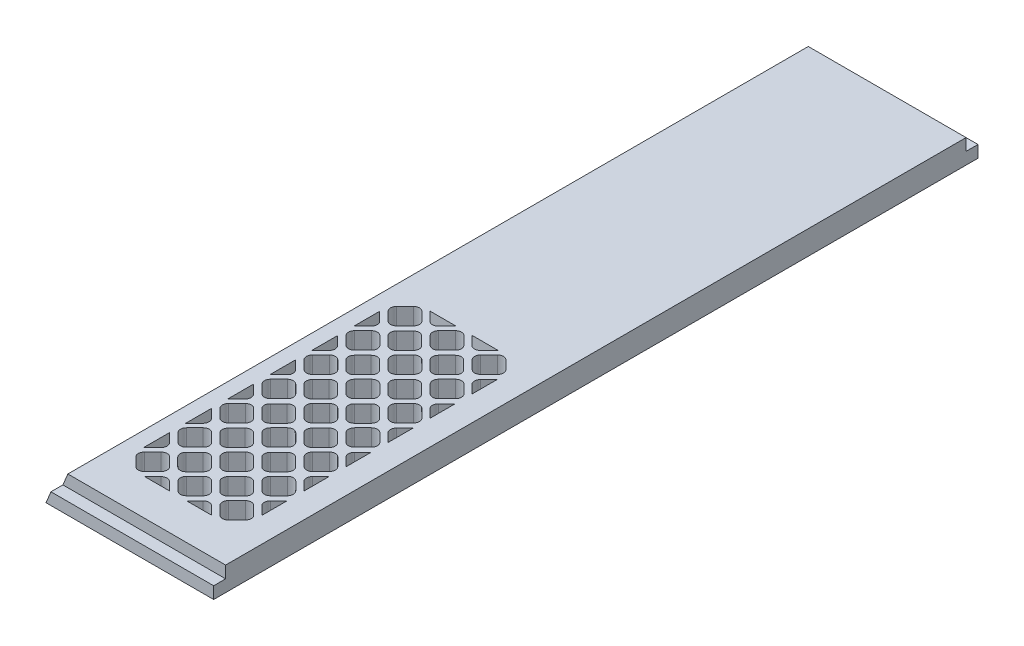
SolidWorks part; units mm, degrees
ref_plane "Front Plane" through (0, 0, 0) normal (0, 0, 1) x (1, 0, 0)
ref_plane "Top Plane" through (0, 0, 0) normal (0, 1, 0) x (1, 0, 0)
ref_plane "Right Plane" through (0, 0, 0) normal (1, 0, 0) x (0, 0, -1)
sketch "Sketch1" plane through (0, 0, 0) normal (0, 0, 1) x (1, 0, 0)
  line L0 (0, 0) -> (5.2605, 12.7)
  line L1 (5.2605, 12.7) -> (89.154, 12.7)
  line L2 (89.154, 12.7) -> (89.154, 0)
  line L3 (89.154, 0) -> (0, 0)
  dimension "D1" = 12.7
  dimension "D2" = 89.154
  dimension "D3" = 67.5
extrude "Boss-Extrude1" add sketch "Sketch1" along normal blind 406.4
sketch "Sketch2" plane through (0, 12.7, 0) normal (0, -1, 0) x (1, 0, 0)
  line L0 (0, 406.4) -> (0, 0) construction
  line L1 (0, 6.35) -> (89.154, 6.35)
  line L2 (0, 6.35) -> (0, 0)
  line L3 (0, 0) -> (89.154, 0)
  line L4 (89.154, 6.35) -> (89.154, 0)
  line L5 (89.154, 406.4) -> (89.154, 0) construction
  line L6 (0, 406.4) -> (89.154, 406.4)
  line L7 (0, 406.4) -> (0, 400.05)
  line L8 (0, 400.05) -> (89.154, 400.05)
  line L9 (89.154, 406.4) -> (89.154, 400.05)
  dimension "D1" = 6.35
  dimension "D2" = 6.35
extrude "Cut-Extrude1" cut sketch "Sketch2" along normal blind 6.35
sketch "Sketch3" plane through (0, 0, 0) normal (0, -1, 0) x (1, 0, 0)
  line L90 (0, 203.2) -> (89.154, 203.2) construction
  line L91 (0, 406.4) -> (0, 0) construction
  line L221 (89.154, 406.4) -> (89.154, 0) construction
  line L222 (13.3842, 233.4919) -> (17.8743, 229.0018)
  line L223 (17.8743, 246.8637) -> (13.3842, 242.3736)
  line L235 (13.3842, 255.8439) -> (17.8743, 251.3538)
  line L236 (17.8743, 269.2157) -> (13.3842, 264.7256)
  line L237 (13.3842, 278.1959) -> (17.8743, 273.7058)
  line L238 (17.8743, 291.5677) -> (13.3842, 287.0776)
  line L239 (13.3842, 300.5479) -> (17.8743, 296.0578)
  line L240 (17.8743, 313.9197) -> (13.3842, 309.4296)
  line L241 (13.3842, 322.8999) -> (17.8743, 318.4098)
  line L242 (17.8743, 336.2717) -> (13.3842, 331.7816)
  line L243 (13.3842, 345.2519) -> (17.8743, 340.7618)
  line L244 (17.8743, 358.6237) -> (13.3842, 354.1336)
  line L245 (13.3842, 367.6039) -> (17.8743, 363.1138)
  line L246 (71.4599, 229.0018) -> (75.9093, 233.4512)
  line L247 (49.1079, 229.0018) -> (53.598, 233.4919)
  line L248 (58.0882, 233.4919) -> (62.5783, 229.0018)
  line L249 (26.7559, 229.0018) -> (31.246, 233.4919)
  line L250 (35.7362, 233.4919) -> (40.2263, 229.0018)
  line L251 (71.4599, 251.3538) -> (75.9093, 255.8032)
  line L252 (75.9093, 242.4143) -> (71.4599, 246.8637)
  line L253 (49.1079, 251.3538) -> (53.598, 255.8439)
  line L254 (53.598, 242.3736) -> (49.1079, 246.8637)
  line L255 (62.5783, 246.8637) -> (58.0882, 242.3736)
  line L256 (58.0882, 255.8439) -> (62.5783, 251.3538)
  line L257 (26.7559, 251.3538) -> (31.246, 255.8439)
  line L258 (31.246, 242.3736) -> (26.7559, 246.8637)
  line L259 (40.2263, 246.8637) -> (35.7362, 242.3736)
  line L260 (35.7362, 255.8439) -> (40.2263, 251.3538)
  line L261 (71.4599, 273.7058) -> (75.9093, 278.1552)
  line L262 (75.9093, 264.7663) -> (71.4599, 269.2157)
  line L263 (49.1079, 273.7058) -> (53.598, 278.1959)
  line L264 (53.598, 264.7256) -> (49.1079, 269.2157)
  line L265 (62.5783, 269.2157) -> (58.0882, 264.7256)
  line L266 (58.0882, 278.1959) -> (62.5783, 273.7058)
  line L267 (26.7559, 273.7058) -> (31.246, 278.1959)
  line L268 (31.246, 264.7256) -> (26.7559, 269.2157)
  line L269 (40.2263, 269.2157) -> (35.7362, 264.7256)
  line L270 (35.7362, 278.1959) -> (40.2263, 273.7058)
  line L271 (71.4599, 296.0578) -> (75.9093, 300.5072)
  line L272 (75.9093, 287.1183) -> (71.4599, 291.5677)
  line L273 (49.1079, 296.0578) -> (53.598, 300.5479)
  line L274 (53.598, 287.0776) -> (49.1079, 291.5677)
  line L275 (62.5783, 291.5677) -> (58.0882, 287.0776)
  line L276 (58.0882, 300.5479) -> (62.5783, 296.0578)
  line L277 (26.7559, 296.0578) -> (31.246, 300.5479)
  line L278 (31.246, 287.0776) -> (26.7559, 291.5677)
  line L279 (40.2263, 291.5677) -> (35.7362, 287.0776)
  line L280 (35.7362, 300.5479) -> (40.2263, 296.0578)
  line L281 (71.4599, 318.4098) -> (75.9093, 322.8592)
  line L282 (75.9093, 309.4703) -> (71.4599, 313.9197)
  line L283 (49.1079, 318.4098) -> (53.598, 322.8999)
  line L284 (53.598, 309.4296) -> (49.1079, 313.9197)
  line L285 (62.5783, 313.9197) -> (58.0882, 309.4296)
  line L286 (58.0882, 322.8999) -> (62.5783, 318.4098)
  line L287 (26.7559, 318.4098) -> (31.246, 322.8999)
  line L288 (31.246, 309.4296) -> (26.7559, 313.9197)
  line L289 (40.2263, 313.9197) -> (35.7362, 309.4296)
  line L290 (35.7362, 322.8999) -> (40.2263, 318.4098)
  line L291 (71.4599, 340.7618) -> (75.9093, 345.2112)
  line L292 (75.9093, 331.8223) -> (71.4599, 336.2717)
  line L293 (49.1079, 340.7618) -> (53.598, 345.2519)
  line L294 (53.598, 331.7816) -> (49.1079, 336.2717)
  line L295 (62.5783, 336.2717) -> (58.0882, 331.7816)
  line L296 (58.0882, 345.2519) -> (62.5783, 340.7618)
  line L297 (26.7559, 340.7618) -> (31.246, 345.2519)
  line L298 (31.246, 331.7816) -> (26.7559, 336.2717)
  line L299 (40.2263, 336.2717) -> (35.7362, 331.7816)
  line L300 (35.7362, 345.2519) -> (40.2263, 340.7618)
  line L301 (71.4599, 363.1138) -> (75.9093, 367.5632)
  line L302 (75.9093, 354.1743) -> (71.4599, 358.6237)
  line L303 (49.1079, 363.1138) -> (53.598, 367.6039)
  line L304 (53.598, 354.1336) -> (49.1079, 358.6237)
  line L305 (62.5783, 358.6237) -> (58.0882, 354.1336)
  line L306 (58.0882, 367.6039) -> (62.5783, 363.1138)
  line L307 (26.7559, 363.1138) -> (31.246, 367.6039)
  line L308 (31.246, 354.1336) -> (26.7559, 358.6237)
  line L309 (40.2263, 358.6237) -> (35.7362, 354.1336)
  line L310 (35.7362, 367.6039) -> (40.2263, 363.1138)
  line L311 (75.9093, 376.5263) -> (71.5993, 380.8363)
  line L312 (53.598, 376.4856) -> (49.2473, 380.8363)
  line L313 (62.4389, 380.8363) -> (58.0882, 376.4856)
  line L314 (31.246, 376.4856) -> (26.8953, 380.8363)
  line L315 (40.0869, 380.8363) -> (35.7362, 376.4856)
  line L316 (17.7349, 380.8363) -> (13.3842, 376.4856)
  line L317 (73.6642, 235.4989) -> (69.1741, 231.0088)
  line L318 (69.1741, 244.4792) -> (73.6642, 239.9891)
  line L319 (60.1938, 239.9891) -> (64.6839, 244.4792)
  line L320 (64.6839, 231.0088) -> (60.1938, 235.4989)
  line L321 (51.3122, 235.4989) -> (46.8221, 231.0088)
  line L322 (46.8221, 244.4792) -> (51.3122, 239.9891)
  line L323 (37.8418, 239.9891) -> (42.3319, 244.4792)
  line L324 (42.3319, 231.0088) -> (37.8418, 235.4989)
  line L325 (28.9602, 235.4989) -> (24.4701, 231.0088)
  line L326 (24.4701, 244.4792) -> (28.9602, 239.9891)
  line L327 (15.4898, 239.9891) -> (19.9799, 244.4792)
  line L328 (19.9799, 231.0088) -> (15.4898, 235.4989)
  line L329 (73.6642, 257.8509) -> (69.1741, 253.3608)
  line L330 (69.1741, 266.8312) -> (73.6642, 262.3411)
  line L331 (60.1938, 262.3411) -> (64.6839, 266.8312)
  line L332 (64.6839, 253.3608) -> (60.1938, 257.8509)
  line L333 (51.3122, 257.8509) -> (46.8221, 253.3608)
  line L334 (46.8221, 266.8312) -> (51.3122, 262.3411)
  line L335 (37.8418, 262.3411) -> (42.3319, 266.8312)
  line L336 (42.3319, 253.3608) -> (37.8418, 257.8509)
  line L337 (28.9602, 257.8509) -> (24.4701, 253.3608)
  line L338 (24.4701, 266.8312) -> (28.9602, 262.3411)
  line L339 (15.4898, 262.3411) -> (19.9799, 266.8312)
  line L340 (19.9799, 253.3608) -> (15.4898, 257.8509)
  line L341 (73.6642, 280.2029) -> (69.1741, 275.7128)
  line L342 (69.1741, 289.1832) -> (73.6642, 284.6931)
  line L343 (60.1938, 284.6931) -> (64.6839, 289.1832)
  line L344 (64.6839, 275.7128) -> (60.1938, 280.2029)
  line L345 (51.3122, 280.2029) -> (46.8221, 275.7128)
  line L346 (46.8221, 289.1832) -> (51.3122, 284.6931)
  line L347 (37.8418, 284.6931) -> (42.3319, 289.1832)
  line L348 (42.3319, 275.7128) -> (37.8418, 280.2029)
  line L349 (28.9602, 280.2029) -> (24.4701, 275.7128)
  line L350 (24.4701, 289.1832) -> (28.9602, 284.6931)
  line L351 (15.4898, 284.6931) -> (19.9799, 289.1832)
  line L352 (19.9799, 275.7128) -> (15.4898, 280.2029)
  line L353 (73.6642, 302.5549) -> (69.1741, 298.0648)
  line L354 (69.1741, 311.5352) -> (73.6642, 307.0451)
  line L355 (60.1938, 307.0451) -> (64.6839, 311.5352)
  line L356 (64.6839, 298.0648) -> (60.1938, 302.5549)
  line L357 (51.3122, 302.5549) -> (46.8221, 298.0648)
  line L358 (46.8221, 311.5352) -> (51.3122, 307.0451)
  line L359 (37.8418, 307.0451) -> (42.3319, 311.5352)
  line L360 (42.3319, 298.0648) -> (37.8418, 302.5549)
  line L361 (28.9602, 302.5549) -> (24.4701, 298.0648)
  line L362 (24.4701, 311.5352) -> (28.9602, 307.0451)
  line L363 (15.4898, 307.0451) -> (19.9799, 311.5352)
  line L364 (19.9799, 298.0648) -> (15.4898, 302.5549)
  line L365 (73.6642, 324.9069) -> (69.1741, 320.4168)
  line L366 (69.1741, 333.8872) -> (73.6642, 329.3971)
  line L367 (60.1938, 329.3971) -> (64.6839, 333.8872)
  line L368 (64.6839, 320.4168) -> (60.1938, 324.9069)
  line L369 (51.3122, 324.9069) -> (46.8221, 320.4168)
  line L370 (46.8221, 333.8872) -> (51.3122, 329.3971)
  line L371 (37.8418, 329.3971) -> (42.3319, 333.8872)
  line L372 (42.3319, 320.4168) -> (37.8418, 324.9069)
  line L373 (28.9602, 324.9069) -> (24.4701, 320.4168)
  line L374 (24.4701, 333.8872) -> (28.9602, 329.3971)
  line L375 (15.4898, 329.3971) -> (19.9799, 333.8872)
  line L376 (19.9799, 320.4168) -> (15.4898, 324.9069)
  line L377 (73.6642, 347.2589) -> (69.1741, 342.7688)
  line L378 (69.1741, 356.2392) -> (73.6642, 351.7491)
  line L379 (60.1938, 351.7491) -> (64.6839, 356.2392)
  line L380 (64.6839, 342.7688) -> (60.1938, 347.2589)
  line L381 (51.3122, 347.2589) -> (46.8221, 342.7688)
  line L382 (46.8221, 356.2392) -> (51.3122, 351.7491)
  line L383 (37.8418, 351.7491) -> (42.3319, 356.2392)
  line L384 (42.3319, 342.7688) -> (37.8418, 347.2589)
  line L385 (28.9602, 347.2589) -> (24.4701, 342.7688)
  line L386 (24.4701, 356.2392) -> (28.9602, 351.7491)
  line L387 (15.4898, 351.7491) -> (19.9799, 356.2392)
  line L388 (19.9799, 342.7688) -> (15.4898, 347.2589)
  line L389 (73.6642, 369.6109) -> (69.1741, 365.1208)
  line L390 (69.1741, 378.5912) -> (73.6642, 374.1011)
  line L391 (60.1938, 374.1011) -> (64.6839, 378.5912)
  line L392 (64.6839, 365.1208) -> (60.1938, 369.6109)
  line L393 (51.3122, 369.6109) -> (46.8221, 365.1208)
  line L394 (46.8221, 378.5912) -> (51.3122, 374.1011)
  line L395 (37.8418, 374.1011) -> (42.3319, 378.5912)
  line L396 (42.3319, 365.1208) -> (37.8418, 369.6109)
  line L397 (19.9799, 365.1208) -> (15.4898, 369.6109)
  line L398 (28.9602, 369.6109) -> (24.4701, 365.1208)
  line L399 (24.4701, 378.5912) -> (28.9602, 374.1011)
  line L400 (75.9093, 380.8363) -> (75.9093, 228.7637)
  line L401 (13.2447, 228.7637) -> (75.9093, 228.7637)
  line L402 (13.2447, 380.8363) -> (13.2447, 228.7637)
  line L403 (13.2447, 380.8363) -> (75.9093, 380.8363)
  line L404 (15.4898, 374.1011) -> (19.9799, 378.5912)
  arc A212 (18.0894, 228.7637) -> (17.8743, 229.0018) centre (15.6292, 226.7568) ccw
  arc A224 (13.2447, 233.6232) -> (13.3842, 233.4919) centre (11.1391, 231.2469) cw
  arc A225 (13.3842, 242.3736) -> (13.2447, 242.2423) centre (11.1391, 244.6186) cw
  arc A226 (17.8743, 246.8637) -> (17.8743, 251.3538) centre (15.6292, 249.1088) ccw
  arc A227 (13.2447, 255.9752) -> (13.3842, 255.8439) centre (11.1391, 253.5989) cw
  arc A228 (13.3842, 264.7256) -> (13.2447, 264.5943) centre (11.1391, 266.9706) cw
  arc A229 (17.8743, 269.2157) -> (17.8743, 273.7058) centre (15.6292, 271.4608) ccw
  arc A230 (13.2447, 278.3272) -> (13.3842, 278.1959) centre (11.1391, 275.9509) cw
  arc A231 (13.3842, 287.0776) -> (13.2447, 286.9463) centre (11.1391, 289.3226) cw
  arc A232 (17.8743, 291.5677) -> (17.8743, 296.0578) centre (15.6292, 293.8128) ccw
  arc A233 (13.2447, 300.6792) -> (13.3842, 300.5479) centre (11.1391, 298.3029) cw
  arc A234 (13.3842, 309.4296) -> (13.2447, 309.2983) centre (11.1391, 311.6746) cw
  arc A235 (17.8743, 313.9197) -> (17.8743, 318.4098) centre (15.6292, 316.1648) ccw
  arc A236 (13.2447, 323.0312) -> (13.3842, 322.8999) centre (11.1391, 320.6549) cw
  arc A237 (13.3842, 331.7816) -> (13.2447, 331.6503) centre (11.1391, 334.0266) cw
  arc A238 (17.8743, 336.2717) -> (17.8743, 340.7618) centre (15.6292, 338.5168) ccw
  arc A239 (13.2447, 345.3832) -> (13.3842, 345.2519) centre (11.1391, 343.0069) cw
  arc A240 (13.3842, 354.1336) -> (13.2447, 354.0023) centre (11.1391, 356.3786) cw
  arc A241 (17.8743, 358.6237) -> (17.8743, 363.1138) centre (15.6292, 360.8688) ccw
  arc A242 (13.2447, 367.7352) -> (13.3842, 367.6039) centre (11.1391, 365.3589) cw
  arc A243 (71.2448, 228.7637) -> (71.4599, 229.0018) centre (73.705, 226.7568) cw
  arc A244 (48.8928, 228.7637) -> (49.1079, 229.0018) centre (51.353, 226.7568) cw
  arc A245 (62.7934, 228.7637) -> (62.5783, 229.0018) centre (60.3332, 226.7568) ccw
  arc A246 (53.598, 233.4919) -> (58.0882, 233.4919) centre (55.8431, 231.2469) cw
  arc A247 (26.5408, 228.7637) -> (26.7559, 229.0018) centre (29.001, 226.7568) cw
  arc A248 (40.4414, 228.7637) -> (40.2263, 229.0018) centre (37.9812, 226.7568) ccw
  arc A249 (31.246, 233.4919) -> (35.7362, 233.4919) centre (33.4911, 231.2469) cw
  arc A250 (71.4599, 246.8637) -> (71.4599, 251.3538) centre (73.705, 249.1088) cw
  arc A251 (49.1079, 246.8637) -> (49.1079, 251.3538) centre (51.353, 249.1088) cw
  arc A252 (58.0882, 242.3736) -> (53.598, 242.3736) centre (55.8431, 244.6186) cw
  arc A253 (62.5783, 246.8637) -> (62.5783, 251.3538) centre (60.3332, 249.1088) ccw
  arc A254 (53.598, 255.8439) -> (58.0882, 255.8439) centre (55.8431, 253.5989) cw
  arc A255 (26.7559, 246.8637) -> (26.7559, 251.3538) centre (29.001, 249.1088) cw
  arc A256 (35.7362, 242.3736) -> (31.246, 242.3736) centre (33.4911, 244.6186) cw
  arc A257 (40.2263, 246.8637) -> (40.2263, 251.3538) centre (37.9812, 249.1088) ccw
  arc A258 (31.246, 255.8439) -> (35.7362, 255.8439) centre (33.4911, 253.5989) cw
  arc A259 (71.4599, 269.2157) -> (71.4599, 273.7058) centre (73.705, 271.4608) cw
  arc A260 (49.1079, 269.2157) -> (49.1079, 273.7058) centre (51.353, 271.4608) cw
  arc A261 (58.0882, 264.7256) -> (53.598, 264.7256) centre (55.8431, 266.9706) cw
  arc A262 (62.5783, 269.2157) -> (62.5783, 273.7058) centre (60.3332, 271.4608) ccw
  arc A263 (53.598, 278.1959) -> (58.0882, 278.1959) centre (55.8431, 275.9509) cw
  arc A264 (26.7559, 269.2157) -> (26.7559, 273.7058) centre (29.001, 271.4608) cw
  arc A265 (35.7362, 264.7256) -> (31.246, 264.7256) centre (33.4911, 266.9706) cw
  arc A266 (40.2263, 269.2157) -> (40.2263, 273.7058) centre (37.9812, 271.4608) ccw
  arc A267 (31.246, 278.1959) -> (35.7362, 278.1959) centre (33.4911, 275.9509) cw
  arc A268 (71.4599, 291.5677) -> (71.4599, 296.0578) centre (73.705, 293.8128) cw
  arc A269 (49.1079, 291.5677) -> (49.1079, 296.0578) centre (51.353, 293.8128) cw
  arc A270 (58.0882, 287.0776) -> (53.598, 287.0776) centre (55.8431, 289.3226) cw
  arc A271 (62.5783, 291.5677) -> (62.5783, 296.0578) centre (60.3332, 293.8128) ccw
  arc A272 (53.598, 300.5479) -> (58.0882, 300.5479) centre (55.8431, 298.3029) cw
  arc A273 (26.7559, 291.5677) -> (26.7559, 296.0578) centre (29.001, 293.8128) cw
  arc A274 (35.7362, 287.0776) -> (31.246, 287.0776) centre (33.4911, 289.3226) cw
  arc A275 (40.2263, 291.5677) -> (40.2263, 296.0578) centre (37.9812, 293.8128) ccw
  arc A276 (31.246, 300.5479) -> (35.7362, 300.5479) centre (33.4911, 298.3029) cw
  arc A277 (71.4599, 313.9197) -> (71.4599, 318.4098) centre (73.705, 316.1648) cw
  arc A278 (49.1079, 313.9197) -> (49.1079, 318.4098) centre (51.353, 316.1648) cw
  arc A279 (58.0882, 309.4296) -> (53.598, 309.4296) centre (55.8431, 311.6746) cw
  arc A280 (62.5783, 313.9197) -> (62.5783, 318.4098) centre (60.3332, 316.1648) ccw
  arc A281 (53.598, 322.8999) -> (58.0882, 322.8999) centre (55.8431, 320.6549) cw
  arc A282 (26.7559, 313.9197) -> (26.7559, 318.4098) centre (29.001, 316.1648) cw
  arc A283 (35.7362, 309.4296) -> (31.246, 309.4296) centre (33.4911, 311.6746) cw
  arc A284 (40.2263, 313.9197) -> (40.2263, 318.4098) centre (37.9812, 316.1648) ccw
  arc A285 (31.246, 322.8999) -> (35.7362, 322.8999) centre (33.4911, 320.6549) cw
  arc A286 (71.4599, 336.2717) -> (71.4599, 340.7618) centre (73.705, 338.5168) cw
  arc A287 (49.1079, 336.2717) -> (49.1079, 340.7618) centre (51.353, 338.5168) cw
  arc A288 (58.0882, 331.7816) -> (53.598, 331.7816) centre (55.8431, 334.0266) cw
  arc A289 (62.5783, 336.2717) -> (62.5783, 340.7618) centre (60.3332, 338.5168) ccw
  arc A290 (53.598, 345.2519) -> (58.0882, 345.2519) centre (55.8431, 343.0069) cw
  arc A291 (26.7559, 336.2717) -> (26.7559, 340.7618) centre (29.001, 338.5168) cw
  arc A292 (35.7362, 331.7816) -> (31.246, 331.7816) centre (33.4911, 334.0266) cw
  arc A293 (40.2263, 336.2717) -> (40.2263, 340.7618) centre (37.9812, 338.5168) ccw
  arc A294 (31.246, 345.2519) -> (35.7362, 345.2519) centre (33.4911, 343.0069) cw
  arc A295 (71.4599, 358.6237) -> (71.4599, 363.1138) centre (73.705, 360.8688) cw
  arc A296 (49.1079, 358.6237) -> (49.1079, 363.1138) centre (51.353, 360.8688) cw
  arc A297 (58.0882, 354.1336) -> (53.598, 354.1336) centre (55.8431, 356.3786) cw
  arc A298 (62.5783, 358.6237) -> (62.5783, 363.1138) centre (60.3332, 360.8688) ccw
  arc A299 (53.598, 367.6039) -> (58.0882, 367.6039) centre (55.8431, 365.3589) cw
  arc A300 (26.7559, 358.6237) -> (26.7559, 363.1138) centre (29.001, 360.8688) cw
  arc A301 (35.7362, 354.1336) -> (31.246, 354.1336) centre (33.4911, 356.3786) cw
  arc A302 (40.2263, 358.6237) -> (40.2263, 363.1138) centre (37.9812, 360.8688) ccw
  arc A303 (31.246, 367.6039) -> (35.7362, 367.6039) centre (33.4911, 365.3589) cw
  arc A304 (58.0882, 376.4856) -> (53.598, 376.4856) centre (55.8431, 378.7306) cw
  arc A305 (35.7362, 376.4856) -> (31.246, 376.4856) centre (33.4911, 378.7306) cw
  arc A306 (13.3842, 376.4856) -> (13.2447, 376.3543) centre (11.1391, 378.7306) cw
  arc A307 (69.1741, 231.0088) -> (64.6839, 231.0088) centre (66.929, 233.2539) cw
  arc A308 (73.6642, 239.9891) -> (73.6642, 235.4989) centre (71.4191, 237.744) cw
  arc A309 (64.6839, 244.4792) -> (69.1741, 244.4792) centre (66.929, 242.2341) cw
  arc A310 (60.1938, 239.9891) -> (60.1938, 235.4989) centre (62.4389, 237.744) ccw
  arc A311 (46.8221, 231.0088) -> (42.3319, 231.0088) centre (44.577, 233.2539) cw
  arc A312 (51.3122, 239.9891) -> (51.3122, 235.4989) centre (49.0671, 237.744) cw
  arc A313 (42.3319, 244.4792) -> (46.8221, 244.4792) centre (44.577, 242.2341) cw
  arc A314 (37.8418, 239.9891) -> (37.8418, 235.4989) centre (40.0869, 237.744) ccw
  arc A315 (28.9602, 239.9891) -> (28.9602, 235.4989) centre (26.7151, 237.744) cw
  arc A316 (19.9799, 244.4792) -> (24.4701, 244.4792) centre (22.225, 242.2341) cw
  arc A317 (24.4701, 231.0088) -> (19.9799, 231.0088) centre (22.225, 233.2539) cw
  arc A318 (15.4898, 239.9891) -> (15.4898, 235.4989) centre (17.7349, 237.744) ccw
  arc A319 (69.1741, 253.3608) -> (64.6839, 253.3608) centre (66.929, 255.6059) cw
  arc A320 (73.6642, 262.3411) -> (73.6642, 257.8509) centre (71.4191, 260.096) cw
  arc A321 (64.6839, 266.8312) -> (69.1741, 266.8312) centre (66.929, 264.5861) cw
  arc A322 (60.1938, 262.3411) -> (60.1938, 257.8509) centre (62.4389, 260.096) ccw
  arc A323 (46.8221, 253.3608) -> (42.3319, 253.3608) centre (44.577, 255.6059) cw
  arc A324 (51.3122, 262.3411) -> (51.3122, 257.8509) centre (49.0671, 260.096) cw
  arc A325 (42.3319, 266.8312) -> (46.8221, 266.8312) centre (44.577, 264.5861) cw
  arc A326 (37.8418, 262.3411) -> (37.8418, 257.8509) centre (40.0869, 260.096) ccw
  arc A327 (28.9602, 262.3411) -> (28.9602, 257.8509) centre (26.7151, 260.096) cw
  arc A328 (19.9799, 266.8312) -> (24.4701, 266.8312) centre (22.225, 264.5861) cw
  arc A329 (24.4701, 253.3608) -> (19.9799, 253.3608) centre (22.225, 255.6059) cw
  arc A330 (15.4898, 262.3411) -> (15.4898, 257.8509) centre (17.7349, 260.096) ccw
  arc A331 (69.1741, 275.7128) -> (64.6839, 275.7128) centre (66.929, 277.9579) cw
  arc A332 (73.6642, 284.6931) -> (73.6642, 280.2029) centre (71.4191, 282.448) cw
  arc A333 (64.6839, 289.1832) -> (69.1741, 289.1832) centre (66.929, 286.9381) cw
  arc A334 (60.1938, 284.6931) -> (60.1938, 280.2029) centre (62.4389, 282.448) ccw
  arc A335 (46.8221, 275.7128) -> (42.3319, 275.7128) centre (44.577, 277.9579) cw
  arc A336 (51.3122, 284.6931) -> (51.3122, 280.2029) centre (49.0671, 282.448) cw
  arc A337 (42.3319, 289.1832) -> (46.8221, 289.1832) centre (44.577, 286.9381) cw
  arc A338 (37.8418, 284.6931) -> (37.8418, 280.2029) centre (40.0869, 282.448) ccw
  arc A339 (28.9602, 284.6931) -> (28.9602, 280.2029) centre (26.7151, 282.448) cw
  arc A340 (19.9799, 289.1832) -> (24.4701, 289.1832) centre (22.225, 286.9381) cw
  arc A341 (24.4701, 275.7128) -> (19.9799, 275.7128) centre (22.225, 277.9579) cw
  arc A342 (15.4898, 284.6931) -> (15.4898, 280.2029) centre (17.7349, 282.448) ccw
  arc A343 (69.1741, 298.0648) -> (64.6839, 298.0648) centre (66.929, 300.3099) cw
  arc A344 (73.6642, 307.0451) -> (73.6642, 302.5549) centre (71.4191, 304.8) cw
  arc A345 (64.6839, 311.5352) -> (69.1741, 311.5352) centre (66.929, 309.2901) cw
  arc A346 (60.1938, 307.0451) -> (60.1938, 302.5549) centre (62.4389, 304.8) ccw
  arc A347 (46.8221, 298.0648) -> (42.3319, 298.0648) centre (44.577, 300.3099) cw
  arc A348 (51.3122, 307.0451) -> (51.3122, 302.5549) centre (49.0671, 304.8) cw
  arc A349 (42.3319, 311.5352) -> (46.8221, 311.5352) centre (44.577, 309.2901) cw
  arc A350 (37.8418, 307.0451) -> (37.8418, 302.5549) centre (40.0869, 304.8) ccw
  arc A351 (28.9602, 307.0451) -> (28.9602, 302.5549) centre (26.7151, 304.8) cw
  arc A352 (19.9799, 311.5352) -> (24.4701, 311.5352) centre (22.225, 309.2901) cw
  arc A353 (24.4701, 298.0648) -> (19.9799, 298.0648) centre (22.225, 300.3099) cw
  arc A354 (15.4898, 307.0451) -> (15.4898, 302.5549) centre (17.7349, 304.8) ccw
  arc A355 (69.1741, 320.4168) -> (64.6839, 320.4168) centre (66.929, 322.6619) cw
  arc A356 (73.6642, 329.3971) -> (73.6642, 324.9069) centre (71.4191, 327.152) cw
  arc A357 (64.6839, 333.8872) -> (69.1741, 333.8872) centre (66.929, 331.6421) cw
  arc A358 (60.1938, 329.3971) -> (60.1938, 324.9069) centre (62.4389, 327.152) ccw
  arc A359 (46.8221, 320.4168) -> (42.3319, 320.4168) centre (44.577, 322.6619) cw
  arc A360 (51.3122, 329.3971) -> (51.3122, 324.9069) centre (49.0671, 327.152) cw
  arc A361 (42.3319, 333.8872) -> (46.8221, 333.8872) centre (44.577, 331.6421) cw
  arc A362 (37.8418, 329.3971) -> (37.8418, 324.9069) centre (40.0869, 327.152) ccw
  arc A363 (28.9602, 329.3971) -> (28.9602, 324.9069) centre (26.7151, 327.152) cw
  arc A364 (19.9799, 333.8872) -> (24.4701, 333.8872) centre (22.225, 331.6421) cw
  arc A365 (24.4701, 320.4168) -> (19.9799, 320.4168) centre (22.225, 322.6619) cw
  arc A366 (15.4898, 329.3971) -> (15.4898, 324.9069) centre (17.7349, 327.152) ccw
  arc A367 (69.1741, 342.7688) -> (64.6839, 342.7688) centre (66.929, 345.0139) cw
  arc A368 (73.6642, 351.7491) -> (73.6642, 347.2589) centre (71.4191, 349.504) cw
  arc A369 (64.6839, 356.2392) -> (69.1741, 356.2392) centre (66.929, 353.9941) cw
  arc A370 (60.1938, 351.7491) -> (60.1938, 347.2589) centre (62.4389, 349.504) ccw
  arc A371 (46.8221, 342.7688) -> (42.3319, 342.7688) centre (44.577, 345.0139) cw
  arc A372 (51.3122, 351.7491) -> (51.3122, 347.2589) centre (49.0671, 349.504) cw
  arc A373 (42.3319, 356.2392) -> (46.8221, 356.2392) centre (44.577, 353.9941) cw
  arc A374 (37.8418, 351.7491) -> (37.8418, 347.2589) centre (40.0869, 349.504) ccw
  arc A375 (28.9602, 351.7491) -> (28.9602, 347.2589) centre (26.7151, 349.504) cw
  arc A376 (19.9799, 356.2392) -> (24.4701, 356.2392) centre (22.225, 353.9941) cw
  arc A377 (24.4701, 342.7688) -> (19.9799, 342.7688) centre (22.225, 345.0139) cw
  arc A378 (15.4898, 351.7491) -> (15.4898, 347.2589) centre (17.7349, 349.504) ccw
  arc A379 (73.6642, 374.1011) -> (73.6642, 369.6109) centre (71.4191, 371.856) cw
  arc A380 (64.6839, 378.5912) -> (69.1741, 378.5912) centre (66.929, 376.3461) cw
  arc A381 (69.1741, 365.1208) -> (64.6839, 365.1208) centre (66.929, 367.3659) cw
  arc A382 (60.1938, 374.1011) -> (60.1938, 369.6109) centre (62.4389, 371.856) ccw
  arc A383 (51.3122, 374.1011) -> (51.3122, 369.6109) centre (49.0671, 371.856) cw
  arc A384 (42.3319, 378.5912) -> (46.8221, 378.5912) centre (44.577, 376.3461) cw
  arc A385 (46.8221, 365.1208) -> (42.3319, 365.1208) centre (44.577, 367.3659) cw
  arc A386 (37.8418, 374.1011) -> (37.8418, 369.6109) centre (40.0869, 371.856) ccw
  arc A387 (15.4898, 374.1011) -> (15.4898, 369.6109) centre (17.7349, 371.856) ccw
  arc A388 (19.9799, 378.5912) -> (24.4701, 378.5912) centre (22.225, 376.3461) cw
  arc A389 (24.4701, 365.1208) -> (19.9799, 365.1208) centre (22.225, 367.3659) cw
  arc A390 (28.9602, 374.1011) -> (28.9602, 369.6109) centre (26.7151, 371.856) cw
  point P1134 (2.1589, 383.2208)
  point P1135 (11.1391, 392.201)
  point P1136 (20.1194, 383.2208)
  point P1137 (13.2447, 371.856)
  point P1138 (22.225, 380.8363)
  point P1139 (31.2053, 371.856)
extrude "Cut-Extrude2" cut sketch "Sketch3" against normal through all contours A390 L399 A388 L404 A387 L397 A389 L398 | L395 A386 L396 A385 L393 A383 L394 A384 | L391 A382 L392 A381 L389 A379 L390 A380 | A299 L303 A296 L304 A297 L305 A298 L306 | A303 L307 A300 L308 A301 L309 A302 L310 | L387 A378 L388 A377 L385 A375 L386 A376 | L383 A374 L384 A371 L381 A372 L382 A373 | L379 A370 L380 A367 L377 A368 L378 A369 | A290 L293 A287 L294 A288 L295 A289 L296 | A294 L297 A291 L298 A292 L299 A293 L300 | L375 A366 L376 A365 L373 A363 L374 A364 | L371 A362 L372 A359 L369 A360 L370 A361 | L367 A358 L368 A355 L365 A356 L366 A357 | A285 L287 A282 L288 A283 L289 A284 L290 | A281 L283 A278 L284 A279 L285 A280 L286 | L363 A354 L364 A353 L361 A351 L362 A352 | L359 A350 L360 A347 L357 A348 L358 A349 | L355 A346 L356 A343 L353 A344 L354 A345 | A272 L273 A269 L274 A270 L275 A271 L276 | A276 L277 A273 L278 A274 L279 A275 L280 | L351 A342 L352 A341 L349 A339 L350 A340 | L339 A330 L340 A329 L337 A327 L338 A328 | L327 A318 L328 A317 L325 A315 L326 A316 | A258 L257 A255 L258 A256 L259 A257 L260 | A267 L267 A264 L268 A265 L269 A266 L270 | L347 A338 L348 A335 L345 A336 L346 A337 | L335 A326 L336 A323 L333 A324 L334 A325 | L323 A314 L324 A311 L321 A312 L322 A313 | A263 L263 A260 L264 A261 L265 A262 L266 | L343 A334 L344 A331 L341 A332 L342 A333 | L331 A322 L332 A319 L329 A320 L330 A321 | A254 L253 A251 L254 A252 L255 A253 L256 | L319 A310 L320 A307 L317 A308 L318 A309 | A242 L402 A240 L244 A241 L245 | A239 L402 A237 L242 A238 L243 | A236 L402 A234 L240 A235 L241 | A305 L315 L403 L314 | A304 L313 L403 L312 | A295 L302 L400 L301 | A286 L292 L400 L291 | A277 L282 L400 L281 | A268 L272 L400 L271 | A233 L402 A231 L238 A232 L239 | A259 L262 L400 L261 | A250 L252 L400 L251 | A246 L247 A244 L401 A245 L248 | A249 L249 A247 L401 A248 L250 | A227 L402 A225 L223 A226 L235 | A230 L402 A228 L236 A229 L237 region at (15.3646, 0, 249.1088) region at (33.4911, 0, 230.9186) region at (15.3646, 0, 271.4608) region at (55.8431, 0, 230.9186) region at (15.3646, 0, 293.8128) region at (15.3646, 0, 316.1648) region at (73.8533, 0, 249.1088) region at (15.3646, 0, 338.5168) region at (73.8533, 0, 271.4608) region at (15.3646, 0, 360.8688) region at (73.8533, 0, 293.8128) region at (73.8533, 0, 316.1648) region at (33.4911, 0, 378.8153) region at (73.8533, 0, 338.5168) region at (55.8431, 0, 378.8153) region at (73.8533, 0, 360.8688) region at (55.8431, 0, 249.1088) region at (33.4911, 0, 249.1088) region at (55.8431, 0, 271.4608) region at (33.4911, 0, 271.4608) region at (55.8431, 0, 293.8128) region at (33.4911, 0, 293.8128) region at (55.8431, 0, 316.1648) region at (33.4911, 0, 316.1648) region at (55.8431, 0, 338.5168) region at (33.4911, 0, 338.5168) region at (55.8431, 0, 360.8688) region at (33.4911, 0, 360.8688) region at (66.929, 0, 237.744) region at (44.577, 0, 237.744) region at (22.225, 0, 237.744) region at (66.929, 0, 260.096) region at (44.577, 0, 260.096) region at (22.225, 0, 260.096) region at (66.929, 0, 282.448) region at (44.577, 0, 282.448) region at (22.225, 0, 282.448) region at (66.929, 0, 304.8) region at (44.577, 0, 304.8) region at (22.225, 0, 304.8) region at (66.929, 0, 327.152) region at (44.577, 0, 327.152) region at (22.225, 0, 327.152) region at (66.929, 0, 349.504) region at (44.577, 0, 349.504) region at (22.225, 0, 349.504) region at (66.929, 0, 371.856) region at (44.577, 0, 371.856) region at (22.225, 0, 371.856)
